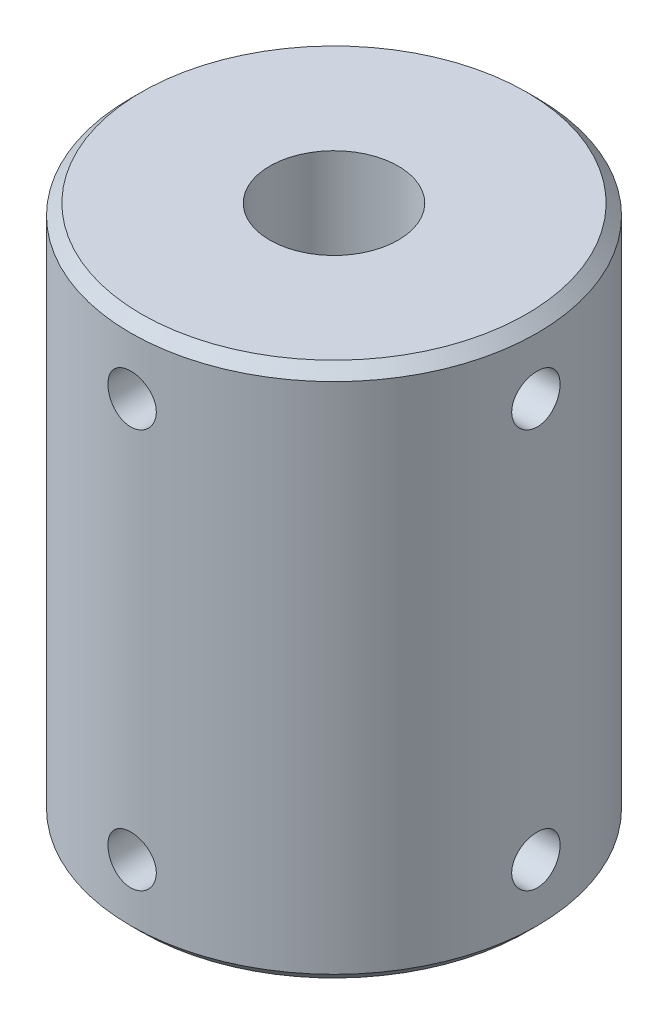
SolidWorks part; units mm, degrees
ref_plane "Front" through (0, 0, 0) normal (0, 0, 1) x (1, 0, 0)
ref_plane "Top" through (0, 0, 0) normal (0, 1, 0) x (1, 0, 0)
ref_plane "Right" through (0, 0, 0) normal (1, 0, 0) x (0, 0, -1)
sketch "Sketch1" plane through (0, 0, 0) normal (0, 1, 0) x (1, 0, 0)
  circle A0 centre (0, 0) radius 9.5
  dimension "D1" = 19
extrude "Boss-Extrude1" add sketch "Sketch1" along normal blind 25
chamfer "Chamfer1" distance 0.508 angle 45 2 edges at (0, 0, 9.5) (0, 25, 9.5)
sketch "Sketch2" plane through (0, 25, 0) normal (0, 1, 0) x (1, 0, 0)
  circle A0 centre (0, 0) radius 3
  dimension "D1" = 6
hole_wizard "Ø6.0mm Dowel Hole1" positions "Sketch3" profile "Sketch4" hole size "Ø6.0" standard "ANSI Metric" end condition through all
sketch "Sketch3" plane through (0, 25, 0) normal (0, 1, 0) x (1, 0, 0)
  point P0 (0, 0)
sketch "Sketch4" plane through (0, 25, 0) normal (1, 0, 0) x (0, 0, 1)
  line L0 (0, 0) -> (0, 25)
  line L1 (0, 25) -> (3, 25)
  line L2 (3, 25) -> (3, 0)
  line L5 (3, 0) -> (0, 0)
  line L11 (0, -6.35) -> (0, 107.95) construction
  dimension "Thru Hole Dia." = 6
  dimension "Thru Hole Depth" = 25
sketch "Sketch5" plane through (0, 0, 0) normal (1, 0, 0) x (0, 0, -1)
  line L0 (0, 0) -> (0, 25) construction
  line L1 (3, 25) -> (-3, 25) construction
  circle A0 centre (0, 21.825) radius 1.5
  circle A1 centre (0, 3.175) radius 1.5
  dimension "D2" = 3
  dimension "D1" = 3.175
  dimension "D3" = 3.175
hole_wizard "#4-40 Tapped Hole1" positions "Sketch6" profile "Sketch7" tap size "#4-40" standard "ANSI Inch" end condition through all
sketch "Sketch6" plane through (0, 0, 0) normal (1, 0, 0) x (0, 0, -1)
  point P0 (0, 21.825)
  point P3 (0, 3.175)
sketch "Sketch7" plane through (0, 21.825, 0) normal (0, 1, 0) x (0, 0, 1)
  line L0 (0, 0) -> (0, 9.5)
  line L1 (0, 9.5) -> (1.1303, 9.5)
  line L2 (1.1303, 9.5) -> (1.1303, 0)
  line L5 (1.1303, 0) -> (0, 0)
  line L11 (0, -6.35) -> (0, 107.95) construction
  dimension "Thru Tap Drill Dia." = 2.2606
  dimension "Thru Tap Drill Depth" = 9.5
cosmetic thread "Hole Thread1" parameters "D2"=2.8448
cosmetic thread "Hole Thread2" parameters "D2"=2.8448
sketch "Sketch8" plane through (0, 0, 0) normal (0, 0, 1) x (1, 0, 0)
  line L0 (0, 1.675) -> (0, 4.675) construction
  line L1 (0, 20.325) -> (0, 23.325) construction
  circle A0 centre (0, 3.175) radius 1.5
  circle A1 centre (0, 21.825) radius 1.5
  dimension "D1" = 3
hole_wizard "#4-40 Tapped Hole2" positions "Sketch9" profile "Sketch10" tap size "#4-40" standard "ANSI Inch" end condition through all
sketch "Sketch9" plane through (0, 0, 0) normal (0, 0, 1) x (1, 0, 0)
  point P0 (0, 21.825)
  point P3 (0, 3.175)
sketch "Sketch10" plane through (0, 21.825, 0) normal (1, 0, 0) x (0, 1, 0)
  line L0 (0, 0) -> (0, 9.5)
  line L1 (0, 9.5) -> (1.1303, 9.5)
  line L2 (1.1303, 9.5) -> (1.1303, 0)
  line L5 (1.1303, 0) -> (0, 0)
  line L11 (0, -6.35) -> (0, 107.95) construction
  dimension "Thru Tap Drill Dia." = 2.2606
  dimension "Thru Tap Drill Depth" = 9.5
cosmetic thread "Hole Thread3" parameters "D2"=2.8448
cosmetic thread "Hole Thread4" parameters "D2"=2.8448
sketch "Sketch11" plane through (0, 0, 0) normal (0, 0, 1) x (1, 0, 0)
  line L0 (-9.5, 24.492) -> (-9.5, 0.508) construction
  line L1 (-9.5, 18.65) -> (-3.15, 18.65)
  line L2 (-9.5, 18.65) -> (-9.5, 17.761)
  line L3 (-9.5, 17.761) -> (-3.15, 17.761)
  line L4 (-3.15, 18.65) -> (-3.15, 17.761)
  line L6 (8.992, 25) -> (-8.992, 25) construction
  point P6 (-9.5, 18.9434)
  dimension "D1" = 0.889
  dimension "D2" = 6.35
  dimension "D3" = 6.35
equation "\"D3@Sketch5\"=\"D1@Sketch5\""
